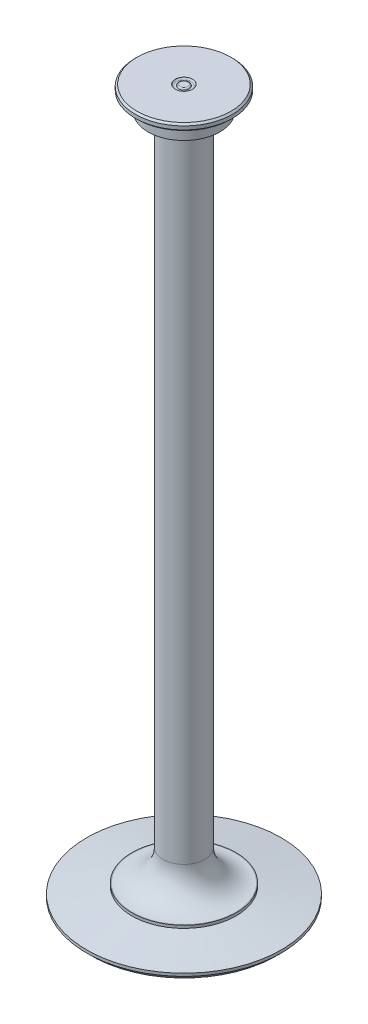
SolidWorks part; units mm, degrees
ref_plane "Alzado" through (0, 0, 0) normal (0, 0, 1) x (1, 0, 0)
ref_plane "Planta" through (0, 0, 0) normal (0, 1, 0) x (1, 0, 0)
ref_plane "Vista lateral" through (0, 0, 0) normal (1, 0, 0) x (0, 0, -1)
sketch "Croquis1" plane through (0, 0, 0) normal (0, 0, 1) x (1, 0, 0)
  line L0 (0, 0) -> (0, 2.7013) construction
  line L1 (-3, 0.98) -> (-7.5, 0.98)
  line L2 (-7.5, 0.98) -> (-14, 0)
  line L3 (-14, 0) -> (0, 0)
  line L4 (0, 2.7013) -> (0, 82.8913) construction
  line L5 (0, 82.8913) -> (-3, 82.8913)
  line L6 (-3, 82.8913) -> (-3, 0.98)
  line L7 (0, 0) -> (0, 82.8913)
  dimension "D1" = 0.98
  dimension "D2" = 14
  dimension "D3" = 6.5
  dimension "D4" = 3
  dimension "D5" = 80.19
revolve "Revolución1" add sketch "Croquis1" angle 360 about L7
sketch "Croquis2" plane through (0, 82.8913, 0) normal (0, 1, 0) x (1, 0, 0)
  circle A1 centre (0, 0) radius 3
  circle A2 centre (0, 0) radius 3
  dimension "D1" = 0
extrude "Saliente-Extruir1" add sketch "Croquis2" along normal blind 17.61
ref_plane "Plano1" through (0, 99.5013, 0) normal (0, 1, 0) x (1, 0, 0)
sketch "Croquis3" plane through (0, 99.5013, 0) normal (0, 1, 0) x (1, 0, 0)
  circle A0 centre (0, 0) radius 7
  circle A1 centre (0, 0) radius 3 construction
  circle A2 centre (0, 0) radius 3
  dimension "D1" = 14
extrude "Saliente-Extruir2" add sketch "Croquis3" along normal up to surface (1 mm away) up to face at (0, 100.5013, 3)
chamfer "Chaflán1" distance 0.25 angle 45 2 edges at (0, 99.5013, 7) (0, 100.5013, 7)
sketch "Croquis4" plane through (0, 0, 0) normal (0, -1, 0) x (1, 0, 0)
  circle A0 centre (0, 0) radius 14 construction
  circle A1 centre (0, 0) radius 14
extrude "Saliente-Extruir3" add sketch "Croquis4" along normal blind 1.5
chamfer "Chaflán2" distance 0.7 angle 45 1 edges at (0, -1.5, -14)
fillet "Redondeo3" radius 4.4 1 edges at (0, 0.98, -3)
sketch "Croquis5" plane through (0, 0, 0) normal (1, 0, 0) x (0, 0, -1)
  line L0 (-7.5, 0.98) -> (-14, 0) construction
  line L1 (-7.5, 0.98) -> (-14, 0)
  line L4 (-7.5, 0.98) -> (-7.5, 0.5826)
  line L5 (-7.5, 0.5826) -> (-14, -0.4)
  line L6 (-14, 0) -> (-14, -0.8) construction
  line L7 (-14, -0.4) -> (-14, 0)
  line L8 (0, 0) -> (0, 6.1693) construction
  dimension "D1" = 0.3974
revolve "Cortar-Revolución1" cut sketch "Croquis5" angle 360 about L8
sketch "Croquis6" plane through (0, 100.5013, 0) normal (0, 1, 0) x (1, 0, 0)
  circle A0 centre (0, 0) radius 1.25
  circle A1 centre (0, 0) radius 0.75
  dimension "D1" = 1.5
  dimension "D2" = 2.5
extrude "Cortar-Extruir1" cut sketch "Croquis6" against normal blind 0.2
fillet "Redondeo4" radius 0.2 1 edges at (0, 100.3013, 1.25)
fillet "Redondeo5" radius 0.2 1 edges at (0, 100.5013, 0.75)
sketch "Croquis7" plane through (0, 99.5013, 0) normal (0, -1, 0) x (1, 0, 0)
  circle A0 centre (0, 0) radius 5.175
  circle A1 centre (0, 0) radius 3 construction
  circle A2 centre (0, 0) radius 3
  dimension "D1" = 10.35
extrude "Saliente-Extruir4" add sketch "Croquis7" along normal blind 2.36
